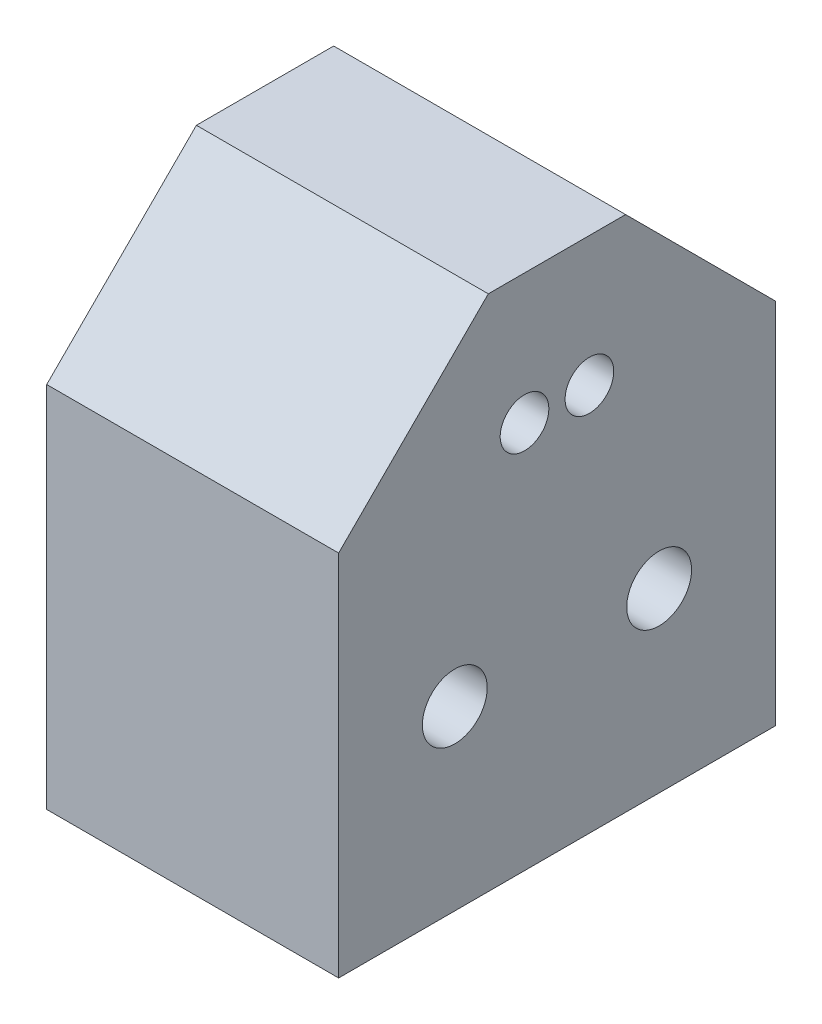
SolidWorks part; units mm, degrees
ref_plane "Front Plane" through (0, 0, 0) normal (0, 0, 1) x (1, 0, 0)
ref_plane "Top Plane" through (0, 0, 0) normal (0, 1, 0) x (1, 0, 0)
ref_plane "Right Plane" through (0, 0, 0) normal (1, 0, 0) x (0, 0, -1)
sketch "Sketch1" plane through (0, 0, 0) normal (1, 0, 0) x (0, 0, -1)
  line L2 (-19.0815, 35.7715) -> (-9.853, 45)
  line L3 (-9.853, 45) -> (-1.3866, 45)
  line L4 (-1.3866, 45) -> (7.8418, 35.7715)
  line L6 (-19.0815, 35.7715) -> (-19.0815, 13.0799)
  line L7 (7.8418, 35.7715) -> (7.8418, 13.0799)
  line L8 (-19.0815, 13.0799) -> (7.8418, 13.0799)
  dimension "D8" = 135
  dimension "D9" = 135
extrude "Boss-Extrude1" add sketch "Sketch1" along normal blind 18
sketch "Sketch2" plane through (18, 0, 0) normal (1, 0, 0) x (0, 0, -1)
  line L0 (-9.853, 45) -> (-9.853, 15.0715) construction
  line L1 (-1.3866, 45) -> (-1.3866, 15.0715) construction
  line L5 (-1.3866, 45) -> (-9.853, 45) construction
  circle A0 centre (-7.6198, 37) radius 1.5
  circle A1 centre (-3.6198, 37) radius 1.5
  circle A2 centre (-11.9198, 24) radius 2
  circle A3 centre (0.6802, 24) radius 2
  point P12 (-1.3866, 45)
  dimension "D1" = 3
  dimension "D2" = 3
  dimension "D5" = 8
  dimension "D3" = 4
  dimension "D4" = 4
  dimension "D10" = 21
  dimension "D11" = 13
  dimension "9.5" = 8
extrude "Cut-Extrude2" cut sketch "Sketch2" against normal through all contours A3 | A0 | A1 | A2 region at (18, 24, -0.6802)
